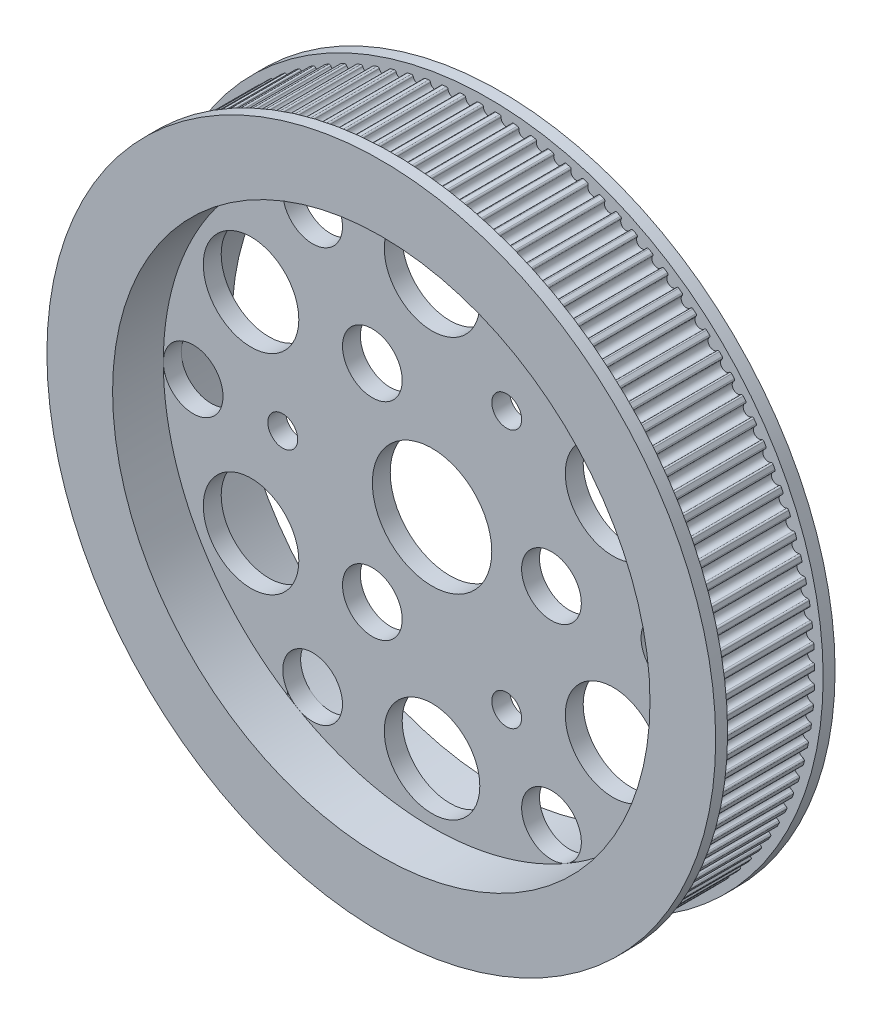
SolidWorks part; units mm, degrees
material "6061-T6 (SS)"
ref_plane "前视基准面" through (0, 0, 0) normal (0, 0, 1) x (1, 0, 0)
ref_plane "上视基准面" through (0, 0, 0) normal (0, 1, 0) x (1, 0, 0)
ref_plane "右视基准面" through (0, 0, 0) normal (1, 0, 0) x (0, 0, -1)
ref_axis "基准轴1" through (0, 0, 55) along (0, 0, -1)
sketch "旋转草图同步带轮01" plane through (0, 0, 0) normal (1, 0, 0) x (0, 0, -1)
  line L0 (0, 0) -> (-18.7856, 0) construction
  line L1 (8, 0) -> (8, 53.4085)
  line L2 (8, 53.4085) -> (7.2619, 53.4085) construction
  line L3 (7.2619, 53.4085) -> (7.2619, 54.7569) construction
  line L4 (7.2619, 54.7569) -> (7.73, 55.8868) construction
  line L5 (7.73, 55.8868) -> (7.026, 56.1785) construction
  line L6 (7.026, 56.1785) -> (6.4999, 54.9085) construction
  line L7 (6.4999, 54.9085) -> (6.4999, 54.591) construction
  line L8 (6.4999, 54.591) -> (-6.4999, 54.591)
  line L9 (-6.4999, 54.591) -> (-6.4999, 54.9085) construction
  line L10 (-6.4999, 54.9085) -> (-7.026, 56.1785) construction
  line L11 (-7.026, 56.1785) -> (-7.73, 55.8868) construction
  line L12 (-7.73, 55.8868) -> (-7.2619, 54.7569) construction
  line L13 (-7.2619, 54.7569) -> (-7.2619, 53.4085) construction
  line L14 (-7.2619, 53.4085) -> (-8, 53.4085) construction
  line L15 (-8, 53.4085) -> (-8, 0)
  line L16 (-8, 0) -> (8, 0)
  line L18 (-6.4999, 54.591) -> (-8, 54.591)
  line L19 (-8, 54.591) -> (-8, 53.4085)
  line L20 (6.4999, 54.591) -> (8, 54.591)
  line L21 (8, 54.591) -> (8, 53.4085)
  point P23 (0, 0)
  dimension "D1" = 16
  dimension "GearBeltFlange1OutsideLength" = 1.3484
  dimension "GearBeltFlange1X" = 0.468
  dimension "GearBeltFlange1Y" = 1.13
  dimension "GearBeltFlangeThickness" = 0.762
  dimension "GearBeltFlangeInside" = 0.3175
  dimension "GearBeltOutsideDiameter" = 54.591
  dimension "GearBeltFlange2X" = 0.468
revolve "同步带轮01" add sketch "旋转草图同步带轮01" angle 360 about L0
sketch "齿草图同步带轮01" plane through (0, 0, 0) normal (0, 0, 1) x (1, 0, 0)
  line L0 (-1.1581, 54.5787) -> (0, 57.131)
  line L1 (0, 57.131) -> (1.1581, 54.5787)
  arc A0 (1.1581, 54.5787) -> (0.9, 54.326) centre (1.1528, 54.326) ccw
  arc A1 (0.9, 54.326) -> (-0.9, 54.326) centre (0, 54.326) cw
  arc A2 (-0.9, 54.326) -> (-1.1581, 54.5787) centre (-1.1528, 54.326) ccw
  dimension "GearBeltToothR1" = 0.5055
  dimension "GearBeltToothR2" = 1.8
  dimension "GearBeltToothCapX1" = 1.1581
  dimension "GearBeltToothCapY1" = 2.5523
  dimension "GearBeltToothCapX2" = 1.1581
  dimension "GearBeltToothCapY2" = 2.5523
extrude "齿拉伸切除同步带轮01" cut sketch "齿草图同步带轮01" against normal through all both and the other way through all
pattern_circular "齿形同步带轮01" count 115 over 360 about axis through (0, 0, 55) along (0, 0, -1) of "齿拉伸切除同步带轮01"
sketch "孔旋转草图" plane through (0, 0, 0) normal (1, 0, 0) x (0, 0, -1)
  line L0 (-5.274, 0) -> (5.274, 0)
  line L1 (5.274, 0) -> (5.274, 127)
  line L2 (5.274, 127) -> (-5.274, 127)
  line L3 (-5.274, 127) -> (-5.274, 0)
  dimension "TaperSide1" = 127
  dimension "TaperSide2" = 127
sketch "辅助草图同步带轮01" plane through (0, 0, 0) normal (0, 0, 1) x (1, 0, 0)
  circle A0 centre (0, 0) radius 54.9085 construction
  dimension "PitchDiameter" = 109.8169
sketch "草图5" plane through (0, 0, 0) normal (0, 0, 1) x (1, 0, 0)
  circle A0 centre (0, 0) radius 56
  dimension "D1" = 112
extrude "凸台-拉伸1" add sketch "草图5" along normal blind 2 from surface starting at face at (0, 0, 8)
extrude "凸台-拉伸2" add sketch "草图5<2>" against normal blind 2 from surface starting at face at (0, 0, -8)
sketch "草图5<2>" plane through (0, 0, 0) normal (0, 0, 1) x (1, 0, 0) same geometry as "草图5"
sketch "草图7" plane through (0, 0, 0) normal (0, 0, 1) x (1, 0, 0)
  circle A0 centre (0, 0) radius 45
  dimension "D1" = 90
extrude "切除-拉伸2" cut sketch "草图7" against normal blind 8.5 from surface starting at face at (56, 0, 10)
extrude "切除-拉伸3" cut sketch "草图7<2>" along normal blind 8.5 from surface starting at face at (-56, 0, -10)
sketch "草图7<2>" plane through (0, 0, 0) normal (0, 0, 1) x (1, 0, 0) same geometry as "草图7"
sketch "草图8" plane through (0, 0, 1.5) normal (0, 0, 1) x (1, 0, 0)
  line L0 (-25, 0) -> (12.5, 21.6506) construction
  line L1 (-6.25, 10.8253) -> (-28.7087, 49.725) construction
  line L2 (-10, -17.3205) -> (-25, 0) construction
  line L3 (-59.3054, 0) -> (35, 0) construction
  circle A0 centre (0, 0) radius 10
  circle A1 centre (0, 0) radius 25 construction
  circle A2 centre (-25, 0) radius 2.5
  circle A3 centre (12.5, 21.6506) radius 2.5
  circle A4 centre (12.5, -21.6506) radius 2.5
  circle A5 centre (-10, 17.3205) radius 5
  circle A6 centre (20, 0) radius 5
  circle A7 centre (-10, -17.3205) radius 5
  circle A8 centre (-30.3109, -17.5) radius 8
  circle A10 centre (0, 0) radius 35 construction
  circle A11 centre (-30.3109, 17.5) radius 8
  circle A12 centre (0, 35) radius 8
  circle A13 centre (30.3109, 17.5) radius 8
  circle A14 centre (30.3109, -17.5) radius 8
  circle A15 centre (0, -35) radius 8
  circle A16 centre (0, 0) radius 20 construction
  circle A17 centre (-20, 34.641) radius 5
  circle A18 centre (0, 0) radius 40 construction
  circle A19 centre (20, 34.641) radius 5
  circle A20 centre (40, 0) radius 5
  circle A21 centre (20, -34.641) radius 5
  circle A22 centre (-20, -34.641) radius 5
  circle A23 centre (-40, 0) radius 5
  point P12 (0, 0)
  point P21 (0, 0)
  point P37 (0, 0)
  point P52 (0, 0)
  dimension "D1" = 20
  dimension "D2" = 5
  dimension "D4" = 50
  dimension "D5" = 10
  dimension "D7" = 16
  dimension "D8" = 70
  dimension "D10" = 40
  dimension "D11" = 10
  dimension "D12" = 80
  dimension "D9" = 6
  dimension "D13" = 6
  dimension "D3" = 3
  dimension "D6" = 3
extrude "切除-拉伸4" cut sketch "草图8" against normal through all
